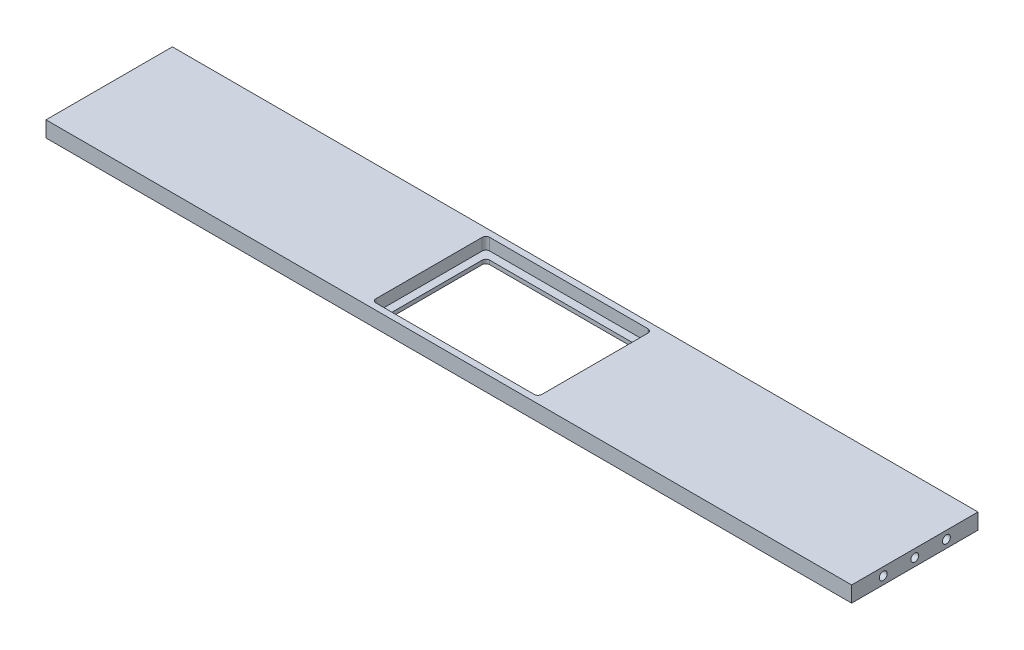
SolidWorks part; units mm, degrees
material "6061 Alloy"
ref_plane "Front" through (0, 0, 0) normal (0, 0, 1) x (1, 0, 0)
ref_plane "Top" through (0, 0, 0) normal (0, 1, 0) x (1, 0, 0)
ref_plane "Right" through (0, 0, 0) normal (1, 0, 0) x (0, 0, -1)
sketch "Sketch2" plane through (0, 0, 0) normal (0, 0, 1) x (1, 0, 0)
  line L5 (0, -12.7) -> (0, 0) construction
  line L9 (-323.85, -12.7) -> (-323.85, 0)
  line L11 (323.85, -12.7) -> (323.85, 0)
  line L15 (-323.85, -12.7) -> (323.85, -12.7)
  line L17 (-323.85, 0) -> (323.85, 0)
  dimension "D3" = 647.7
  dimension "D4" = 12.7
extrude "Boss-Extrude1" add sketch "Sketch2" along normal mid plane 101.6
sketch "Sketch3" plane through (0, 0, 0) normal (0, 1, 0) x (1, 0, 0)
  line L0 (0, -45.72) -> (0, -39.37) construction
  line L1 (63.675, 45.72) -> (-63.675, 45.72)
  line L2 (66.675, 42.72) -> (66.675, -42.72)
  line L3 (63.675, -45.72) -> (-63.675, -45.72)
  line L4 (-66.675, 42.72) -> (-66.675, -42.72)
  line L5 (66.675, 45.72) -> (-66.675, -45.72) construction
  line L6 (66.675, -45.72) -> (-66.675, 45.72) construction
  line L7 (57.325, 39.37) -> (-57.325, 39.37)
  line L8 (60.325, 36.37) -> (60.325, -36.37)
  line L9 (57.325, -39.37) -> (-57.325, -39.37)
  line L10 (-60.325, 36.37) -> (-60.325, -36.37)
  line L11 (0, 39.37) -> (0, 45.72) construction
  arc A0 (63.675, 45.72) -> (66.675, 42.72) centre (63.675, 42.72) cw
  arc A1 (-66.675, 42.72) -> (-63.675, 45.72) centre (-63.675, 42.72) cw
  arc A2 (-63.675, -45.72) -> (-66.675, -42.72) centre (-63.675, -42.72) cw
  arc A3 (66.675, -42.72) -> (63.675, -45.72) centre (63.675, -42.72) cw
  arc A4 (57.325, 39.37) -> (60.325, 36.37) centre (57.325, 36.37) cw
  arc A5 (-57.325, 39.37) -> (-60.325, 36.37) centre (-57.325, 36.37) ccw
  arc A6 (-57.325, -39.37) -> (-60.325, -36.37) centre (-57.325, -36.37) cw
  arc A7 (60.325, -36.37) -> (57.325, -39.37) centre (57.325, -36.37) cw
  point P0 (0, 0)
  point P18 (0, 0)
  dimension "D3" = 3
  dimension "D6" = 3
  dimension "D1" = 133.35
  dimension "D2" = 91.44
  dimension "D4" = 6.35
  dimension "D5" = 6.35
  dimension "D7" = 6.35
extrude "Cut-Extrude1" cut sketch "Sketch3" against normal offset from surface (9.525 mm away) 3.175 contours L3 A2 L4 A1 L1 A0 L2 A3 up to face at (0, -12.7, 0)
hole_wizard "1/4\"-20 threaded hole" positions "Sketch7" profile "Sketch6" hole size "#97" standard "ANSI Inch"
sketch "Sketch7" plane through (-323.85, 0, 0) normal (-1, 0, 0) x (0, 0, 1)
  line L0 (-50.8, -6.35) -> (50.8, -6.35) construction
  line L1 (-50.8, 0) -> (-50.8, -12.7) construction
  line L2 (50.8, 0) -> (50.8, -12.7) construction
  point P0 (-25.4, -6.35)
  point P2 (0, -6.35)
  point P4 (25.4, -6.35)
  dimension "D1" = 25.4
  dimension "D2" = 25.4
sketch "Sketch6" plane through (-323.85, -6.35, -25.4) normal (0, 1, 0) x (0, 0, 1)
  line L0 (0, 0) -> (0, 52.7077)
  line L1 (0, 52.7077) -> (3.175, 50.8)
  line L2 (3.175, 50.8) -> (3.175, 0)
  line L5 (3.175, 0) -> (0, 0)
  line L10 (0, 52.7077) -> (-3.175, 50.8) construction
  line L11 (0, -6.35) -> (0, 107.95) construction
  dimension "Hole Dia." = 6.35
  dimension "Hole Depth" = 50.8
  dimension "Drill Angle" = 118
mirror "Mirror1" about plane through (0, 0, 0) normal (1, 0, 0) of "1/4\"-20 threaded hole"
extrude "Cut-Extrude2" cut sketch "Sketch3<3>" against normal through all contours L9 A6 L10 A5 L7 A4 L8 A7
sketch "Sketch3<3>" plane through (0, 0, 0) normal (0, 1, 0) x (1, 0, 0) same geometry as "Sketch3"
